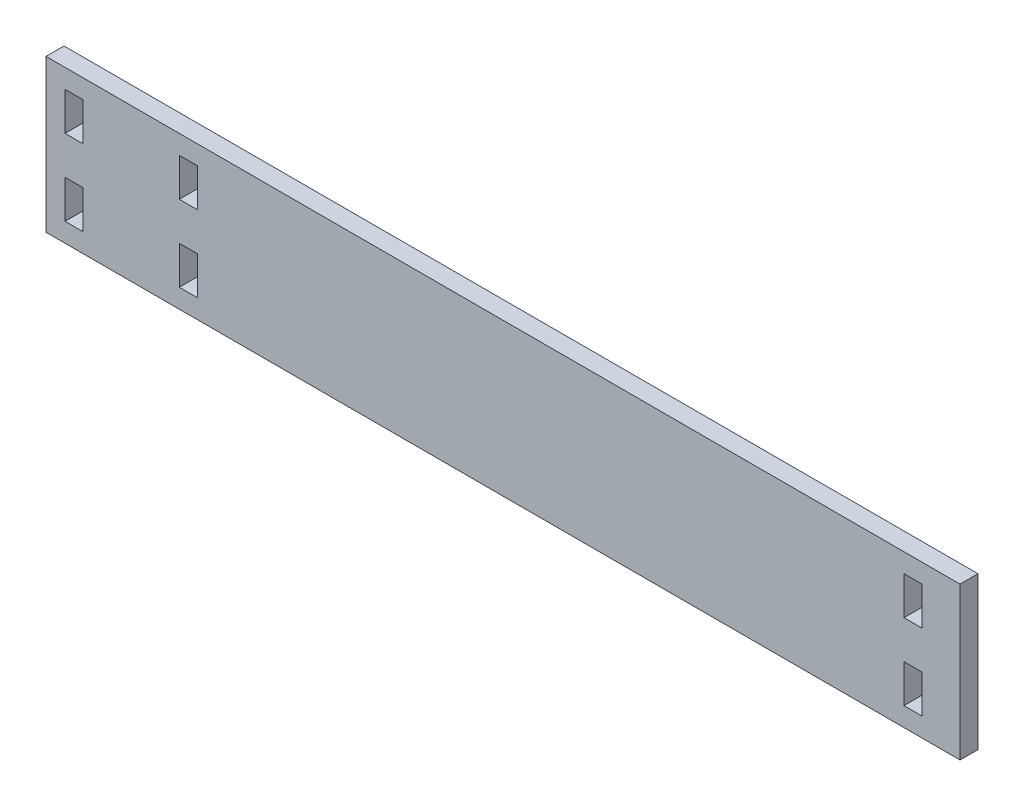
SolidWorks part; units mm, degrees
ref_plane "Front Plane" through (0, 0, 0) normal (0, 0, 1) x (1, 0, 0)
ref_plane "Top Plane" through (0, 0, 0) normal (0, 1, 0) x (1, 0, 0)
ref_plane "Right Plane" through (0, 0, 0) normal (1, 0, 0) x (0, 0, -1)
sketch "Sketch1" plane through (0, 0, 0) normal (0, 0, 1) x (1, 0, 0)
  line L0 (-18.6944, 19.05) -> (-18.6944, 6.35)
  line L1 (0, 0) -> (-304.8, 0)
  line L2 (0, 0) -> (0, 50.8)
  line L3 (0, 50.8) -> (-304.8, 50.8)
  line L4 (-304.8, 0) -> (-304.8, 50.8)
  line L5 (-18.6944, 44.45) -> (-12.7, 44.45)
  line L6 (-18.6944, 44.45) -> (-18.6944, 31.75)
  line L7 (-18.6944, 31.75) -> (-12.7, 31.75)
  line L8 (-12.7, 44.45) -> (-12.7, 31.75)
  line L9 (-18.6944, 19.05) -> (-12.7, 19.05)
  line L10 (-12.7, 19.05) -> (-12.7, 6.35)
  line L11 (-18.6944, 6.35) -> (-12.7, 6.35)
  line L12 (-260.35, 31.75) -> (-254.3556, 31.75)
  line L13 (-260.35, 44.45) -> (-260.35, 31.75)
  line L14 (-260.35, 44.45) -> (-254.3556, 44.45)
  line L15 (-254.3556, 44.45) -> (-254.3556, 31.75)
  line L16 (-260.35, 19.05) -> (-254.3556, 19.05)
  line L17 (-260.35, 19.05) -> (-260.35, 6.35)
  line L18 (-260.35, 6.35) -> (-254.3556, 6.35)
  line L19 (-254.3556, 19.05) -> (-254.3556, 6.35)
  line L20 (-292.4556, 19.05) -> (-292.4556, 6.35)
  line L21 (-298.45, 6.35) -> (-292.4556, 6.35)
  line L22 (-298.45, 19.05) -> (-298.45, 6.35)
  line L23 (-298.45, 19.05) -> (-292.4556, 19.05)
  line L24 (-298.45, 31.75) -> (-292.4556, 31.75)
  line L25 (-298.45, 44.45) -> (-298.45, 31.75)
  line L26 (-298.45, 44.45) -> (-292.4556, 44.45)
  line L27 (-292.4556, 44.45) -> (-292.4556, 31.75)
  dimension "D1" = 50.8
  dimension "D2" = 304.8
  dimension "D3" = 5.9944
  dimension "D4" = 12.7
  dimension "D5" = 6.35
  dimension "D7" = 12.7
  dimension "D9" = 44.45
  dimension "D6" = 2
  dimension "D8" = 2
  dimension "D10" = 2
extrude "Boss-Extrude1" add sketch "Sketch1" along normal blind 5.9944
